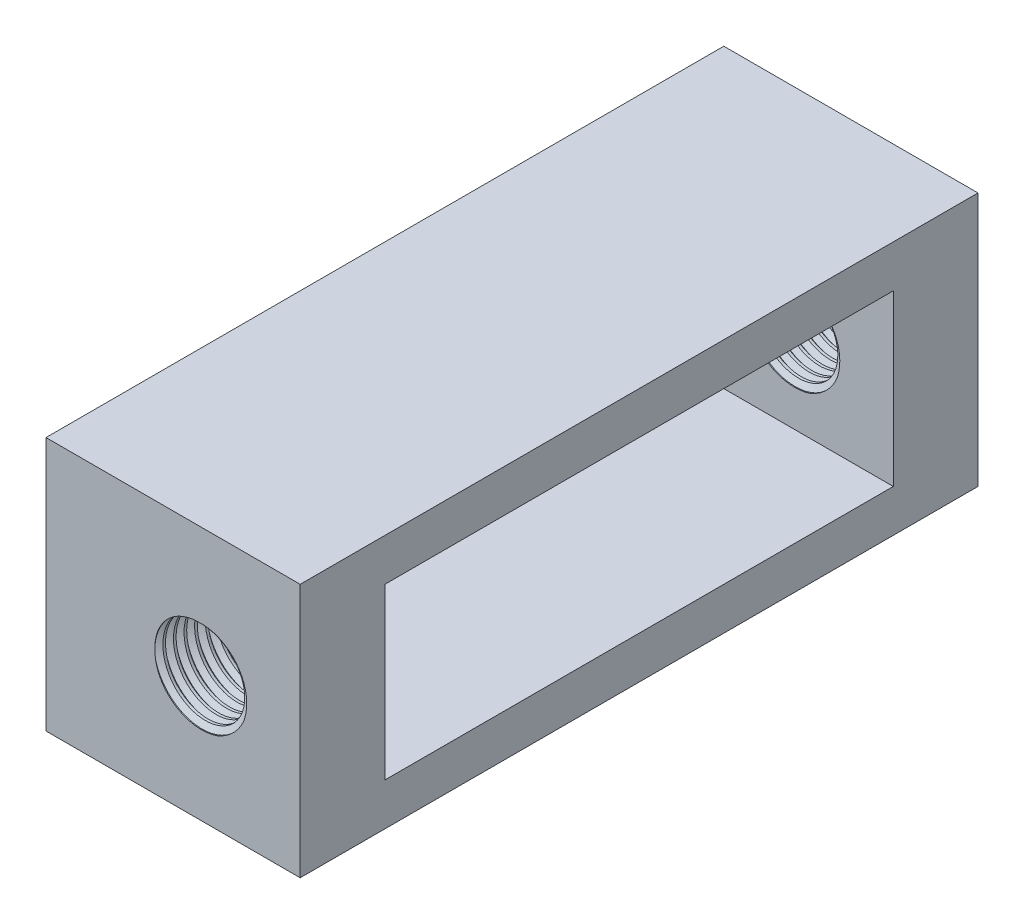
SolidWorks part; units mm, degrees
ref_plane "Front Plane" through (0, 0, 0) normal (0, 0, 1) x (1, 0, 0)
ref_plane "Top Plane" through (0, 0, 0) normal (0, 1, 0) x (1, 0, 0)
ref_plane "Right Plane" through (0, 0, 0) normal (1, 0, 0) x (0, 0, -1)
sketch "Sketch1" plane through (0, 0, 0) normal (0, 0, 1) x (1, 0, 0)
  line L1 (-38.1, 38.1) -> (38.1, 38.1)
  line L2 (-38.1, 38.1) -> (-38.1, -38.1)
  line L3 (-38.1, -38.1) -> (38.1, -38.1)
  line L4 (38.1, 38.1) -> (38.1, -38.1)
  line L5 (-38.1, 38.1) -> (38.1, -38.1) construction
  line L6 (-38.1, -38.1) -> (38.1, 38.1) construction
  point P0 (0, 0)
  dimension "D1" = 76.2
  dimension "D2" = 76.2
extrude "Boss-Extrude1" add sketch "Sketch1" along normal blind 203.2 contours L2 L1 L4 L3
sketch "Sketch5" plane through (38.1, 0, 0) normal (1, 0, 0) x (0, 0, -1)
  line L0 (-203.2, 38.1) -> (-203.2, -38.1) construction
  line L1 (-177.8, 25.4) -> (-25.4, 25.4)
  line L2 (-177.8, 25.4) -> (-177.8, -25.4)
  line L3 (-177.8, -25.4) -> (-25.4, -25.4)
  line L4 (-25.4, 25.4) -> (-25.4, -25.4)
  line L5 (-177.8, 25.4) -> (-25.4, -25.4) construction
  line L6 (-177.8, -25.4) -> (-25.4, 25.4) construction
  line L7 (0, 38.1) -> (0, -38.1) construction
  line L8 (-203.2, 38.1) -> (0, 38.1) construction
  line L9 (-203.2, -38.1) -> (0, -38.1) construction
  point P4 (-101.6, 0)
  point P7 (-203.2, 0)
  dimension "D1" = 25.4
  dimension "D2" = 25.4
  dimension "D3" = 12.7
  dimension "D4" = 12.7
extrude "Cut-Extrude2" cut sketch "Sketch5" against normal blind 50.8
sketch "Sketch6" plane through (0, 0, 0) normal (0, 0, -1) x (-1, 0, 0)
  line L2 (38.1, -38.1) -> (-38.1, -38.1) construction
  line L4 (-38.1, 38.1) -> (-38.1, -38.1) construction
  circle A1 centre (-7.62, 0) radius 13.0579
  point P5 (0, 0)
  point P7 (-38.1, -0.1986)
  dimension "D1" = 38.1
  dimension "D2" = 30.48
extrude "Cut-Extrude3" cut sketch "Sketch6" against normal through all
thread "Thread1" pitch 3.175 profile "Thread Profile1" start angle 0, offset 0, length 254, pitch 3.175, diameter 26.1158
ref_plane "Plane3" through (-5.4379, 0, 177.8) normal (0, -1, 0) x (-1, 0, 0)
sketch "Thread Profile1" plane through (-5.4379, 0, 177.8) normal (0, -1, 0) x (-1, 0, 0)
  line L0 (0, 0) -> (0, 3.175) construction
  line L1 (0, 0) -> (1.7185, 0.9922)
  line L2 (1.7185, 0.9922) -> (1.7185, 1.3891)
  line L3 (1.7185, 1.3891) -> (0, 2.3812)
  line L4 (1.7185, 1.1906) -> (0, 1.1906) construction
  line L11 (0, 0) -> (0, 2.3812)
  point P2 (0, 0)
  dimension "Pitch" = 3.175
  dimension "Profile_Angle" = 60
  dimension "Profile_Land" = 0.3969
  dimension "Profile_Height" = 1.7185
thread "Thread2" pitch 3.175 profile "Thread Profile2" start angle 0, offset 0, length 254, pitch 3.175, diameter 26.1158
ref_plane "Plane4" through (-5.4379, 0, 25.4) normal (0, -1, 0) x (-1, 0, 0)
sketch "Thread Profile2" plane through (-5.4379, 0, 25.4) normal (0, -1, 0) x (-1, 0, 0)
  line L0 (0, 0) -> (0, 3.175) construction
  line L1 (0, 0) -> (1.7185, 0.9922)
  line L2 (1.7185, 0.9922) -> (1.7185, 1.3891)
  line L3 (1.7185, 1.3891) -> (0, 2.3812)
  line L4 (1.7185, 1.1906) -> (0, 1.1906) construction
  line L11 (0, 0) -> (0, 2.3812)
  point P2 (0, 0)
  dimension "Pitch" = 3.175
  dimension "Profile_Angle" = 60
  dimension "Profile_Land" = 0.3969
  dimension "Profile_Height" = 1.7185
